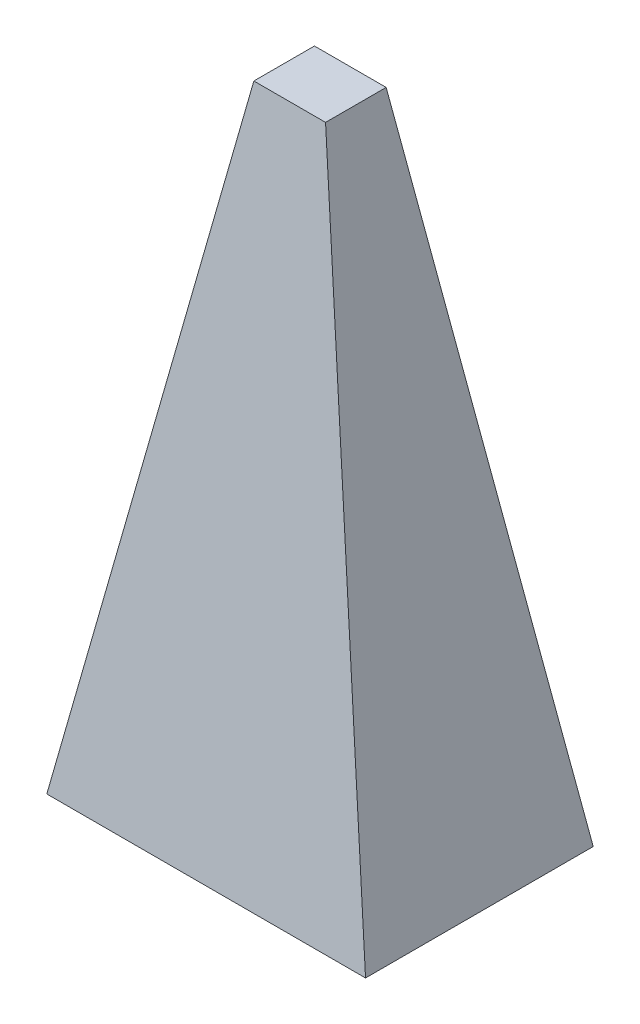
SolidWorks part; units mm, degrees
material "Gray Cast Iron"
ref_plane "Front Plane" through (0, 0, 0) normal (0, 0, 1) x (1, 0, 0)
ref_plane "Top Plane" through (0, 0, 0) normal (0, 1, 0) x (1, 0, 0)
ref_plane "Right Plane" through (0, 0, 0) normal (1, 0, 0) x (0, 0, -1)
sketch "Sketch1" plane through (0, 0, 0) normal (1, 0, 0) x (0, 0, -1)
  line L0 (-31.75, 0) -> (31.75, 0)
  line L1 (31.75, 0) -> (8.45, 177.8)
  line L2 (8.45, 177.8) -> (-8.45, 177.8)
  line L3 (-8.45, 177.8) -> (-31.75, 0)
extrude "Boss-Extrude1" add sketch "Sketch1" along normal mid plane 88.9
sketch "Sketch2" plane through (0, 0, 0) normal (0, 0, 1) x (1, 0, 0)
  line L0 (-44.45, 0) -> (-10, 177.8)
  line L1 (-10, 177.8) -> (-59.45, 177.8)
  line L2 (-59.45, 177.8) -> (-59.45, 0)
  line L3 (-59.45, 0) -> (-44.45, 0)
  line L4 (44.45, 0) -> (10, 177.8)
  line L5 (10, 177.8) -> (59.45, 177.8)
  line L6 (59.45, 177.8) -> (59.45, 0)
  line L7 (59.45, 0) -> (44.45, 0)
extrude "Cut-Extrude1" cut sketch "Sketch2" against normal mid plane 158.75
sketch "Sketch3" plane through (0, 0, 0) normal (0, 1, 0) x (1, 0, 0)
  circle A0 centre (-31.75, 0) radius 3.9688
  circle A1 centre (31.75, 0) radius 3.9687
  dimension "D1" = 7.9375
  dimension "D2" = 7.9375
extrude "Cut-Extrude2" cut sketch "Sketch3" against normal mid plane 50
